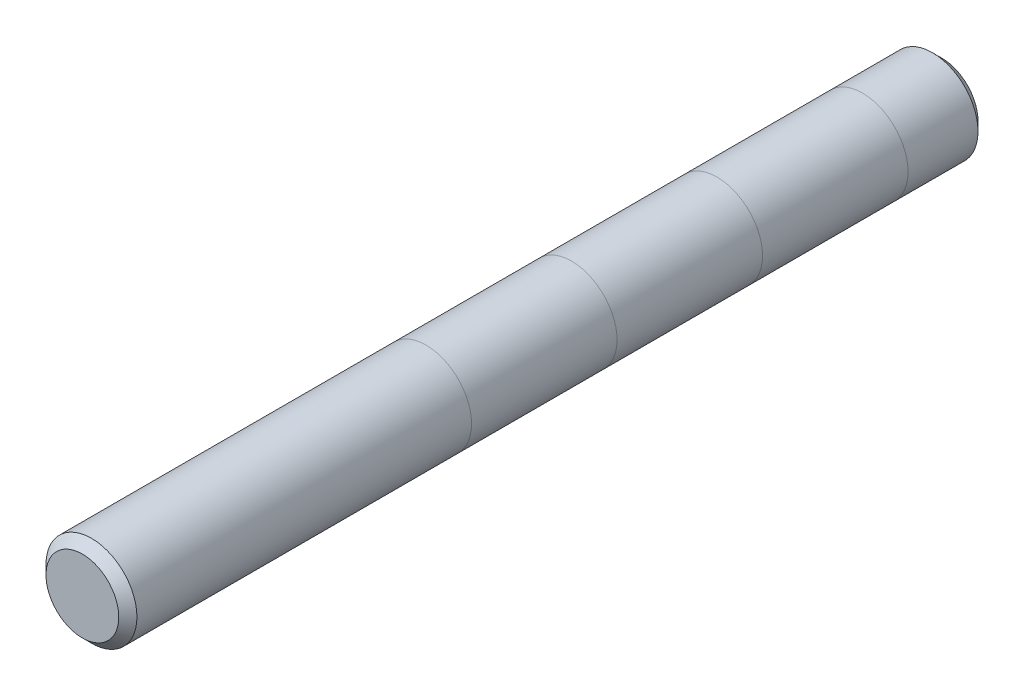
SolidWorks part; units mm, degrees
material "Plain Carbon Steel"
ref_plane "Front" through (0, 0, 0) normal (0, 0, 1) x (1, 0, 0)
ref_plane "Top" through (0, 0, 0) normal (0, 1, 0) x (1, 0, 0)
ref_plane "Right" through (0, 0, 0) normal (1, 0, 0) x (0, 0, -1)
sketch "Sketch1" plane through (0, 0, 0) normal (0, 0, 1) x (1, 0, 0)
  circle A0 centre (0, 0) radius 7.9375
  dimension "Diameter" = 15.875
sketch "Sketch2" plane through (0, 0, 0) normal (1, 0, 0) x (0, 0, -1)
  line L0 (-75, 0) -> (75, 0) construction
  line L1 (-24.2, 7.9375) -> (-24.2, -7.9375) construction
  line L2 (55, 0) -> (-55, 0) construction
  line L3 (24.2, 7.9375) -> (24.2, -7.9375) construction
  line L4 (-75, 7.9375) -> (-75, -7.9375) construction
  line L5 (75, 7.9375) -> (75, -7.9375) construction
  point P3 (-24.2, 0)
  point P8 (0, 0)
  point P9 (24.2, 0)
  point P15 (-75, 0)
  point P18 (75, 0)
  dimension "D1" = 15.875
  dimension "Length" = 150
  dimension "D2" = 50.8
  dimension "D3" = 50.8
sketch "Sketch3" plane through (0, 0, 0) normal (0, 0, 1) x (1, 0, 0)
  circle A0 centre (0, 0) radius 7.9375
  dimension "D1" = 15.875
extrude "Boss-Extrude1" add sketch "Sketch3" along normal mid plane 150
chamfer "Chamfer1" distance 1.5875 angle 45 2 edges at (7.9375, 0, -75) (7.9375, 0, 75)
sketch "Sketch4" plane through (0, 0, 0) normal (1, 0, 0) x (0, 0, -1)
  line L0 (-15, 7.9375) -> (-15, -7.9375)
  line L1 (73.4125, 7.9375) -> (-73.4125, 7.9375) construction
  line L2 (-73.4125, -7.9375) -> (73.4125, -7.9375) construction
  line L3 (10.4, 7.9375) -> (10.4, -7.9375)
  line L4 (-75, 6.35) -> (-75, -6.35) construction
  line L5 (35.8, 7.9375) -> (35.8, -7.9375)
  line L6 (61.2, 7.9375) -> (61.2, -7.9375)
  dimension "D1" = 60
  dimension "D2" = 25.4
  dimension "D3" = 25.4
  dimension "D4" = 25.4
split line "Split Line1"
equation "\"D1@Sketch3\" = \"Diameter@Sketch1\""
equation "\"D1@Boss-Extrude1\" = \"Length@Sketch2\""
equation "\"D1@Chamfer1\" = \"Diameter@Sketch1\" * .1"
equation "\"D1@Sketch2\" = \"Diameter@Sketch1\""
